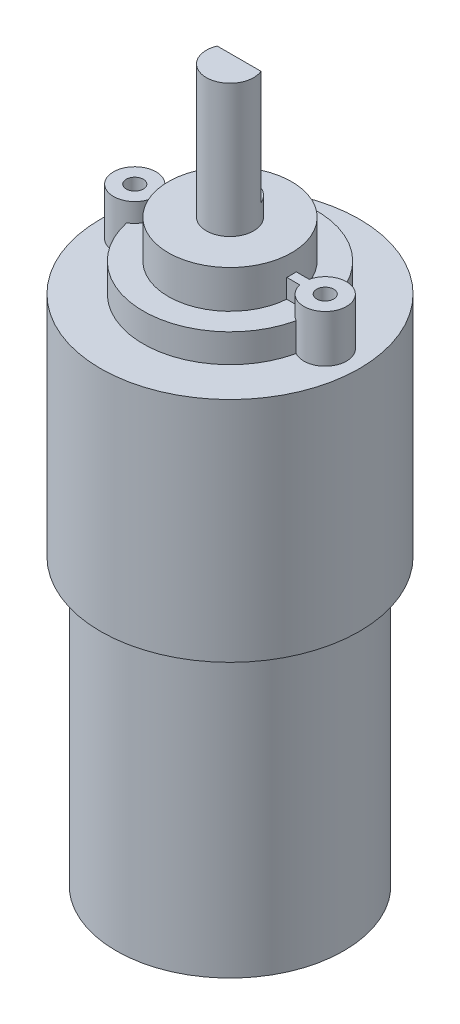
SolidWorks part; units mm, degrees
ref_plane "Alzado" through (0, 0, 0) normal (0, 0, 1) x (1, 0, 0)
ref_plane "Planta" through (0, 0, 0) normal (0, 1, 0) x (1, 0, 0)
ref_plane "Vista lateral" through (0, 0, 0) normal (1, 0, 0) x (0, 0, -1)
sketch "Croquis1" plane through (0, 0, 0) normal (0, 0, 1) x (1, 0, 0)
  line L0 (0, 65.6872) -> (0, -89.1873) construction
  line L1 (0, 30.5) -> (-6.5, 30.5)
  line L2 (-6.5, 30.5) -> (-6.5, 26.5)
  line L3 (-6.5, 26.5) -> (-9.15, 26.5)
  line L4 (-9.15, 26.5) -> (-9.15, 23.5)
  line L5 (-9.15, 23.5) -> (-13.65, 23.5)
  line L6 (-13.65, 23.5) -> (-13.65, -0.5)
  line L7 (-13.65, -0.5) -> (-12, -0.5)
  line L8 (-12, -0.5) -> (-12, -30.5)
  line L9 (-12, -30.5) -> (0, -30.5)
  line L10 (0, -30.5) -> (0, 30.5)
  line L11 (0, 30.5) -> (0, 44.5)
  line L12 (0, 44.5) -> (-2.5, 44.5)
  line L13 (-2.5, 44.5) -> (-2.5, 30.5)
  line L14 (-2.5, 30.5) -> (0, 30.5)
  point P5 (0, 0)
  dimension "D1" = 6.5
  dimension "D2" = 4
  dimension "D3" = 9.15
  dimension "D4" = 13.65
  dimension "D5" = 24
  dimension "D6" = 30
  dimension "D7" = 3
  dimension "D8" = 12
  dimension "D9" = 14
  dimension "D10" = 2.5
revolve "Revolución1" add sketch "Croquis1" angle 360 about L0 region at (-6.2154, -0.52, 0) region at (-1.25, 37.5, 0)
sketch "Croquis2" plane through (0, 44.5, 0) normal (0, 1, 0) x (1, 0, 0)
  line L0 (-2.3083, 0.96) -> (2.3083, 0.96)
  circle A1 centre (0, 0) radius 2.5
  circle A2 centre (0, 0) radius 2.5
  circle M3 centre (0, 0) radius 2.5
  dimension "D2" = 0.96
  dimension "D1" = 0
extrude "Cortar-Extruir1" cut sketch "Croquis2" against normal blind 12 contours L0 M3 region at (0, 44.5, -1.5959)
sketch "Croquis4" plane through (0, 23.5, 0) normal (0, 1, 0) x (1, 0, 0)
  line L0 (0, 5.4331) -> (0, -4.2682) construction
  line L1 (9, 0.5) -> (-9, 0.5)
  line L2 (0, 0.5) -> (0, -0.5)
  line L3 (9, -0.5) -> (-9, -0.5)
  line L4 (-9, 0.5) -> (-9, -0.5)
  line L5 (-12.29, 7.8034) -> (-12.29, -7.8344) construction
  line L6 (0, 0) -> (-16.243, 0) construction
  line L7 (9, 0.5) -> (9, -0.5)
  circle A0 centre (-10.04, 0) radius 2.25
  circle A1 centre (-10.04, 0) radius 0.9
  circle A2 centre (10.04, 0) radius 0.9
  circle A3 centre (10.04, 0) radius 2.25
  point P10 (0, 0)
  circle M11 centre (0, 0) radius 9.15
  dimension "D1" = 1.8
  dimension "D2" = 4.5
  dimension "D3" = 1
  dimension "D4" = 12.29
  dimension "D5" = 9
extrude "Saliente-Extruir1" add sketch "Croquis4" along normal blind 5 contours A1 A0 M11 | A1 A0 L3 L4 L1 M11 | A0 L3 L2 L1 | L3 A3 L1 L2 | A3 A2 L1 L7 L3 M11 | A3 L3 L7 L1 | A3 A2 M11 | L3 A0 L1 L4 region at (8.4042, 23.5, 0) region at (8.4231, 23.5, -0.5413) region at (3.9043, 23.5, 0) region at (-3.9043, 23.5, 0) region at (11.1478, 23.5, -1.8937) region at (-8.4042, 23.5, 0) region at (-8.4231, 23.5, -0.5413) region at (-9.1453, 23.5, -1.0563)
sketch "Croquis5" plane through (0, 23.5, 0) normal (0, 1, 0) x (1, 0, 0)
  circle A1 centre (0, 0) radius 13.65
  circle A2 centre (0, 0) radius 13.65
  dimension "D2" = 27.3
  dimension "D1" = 0
